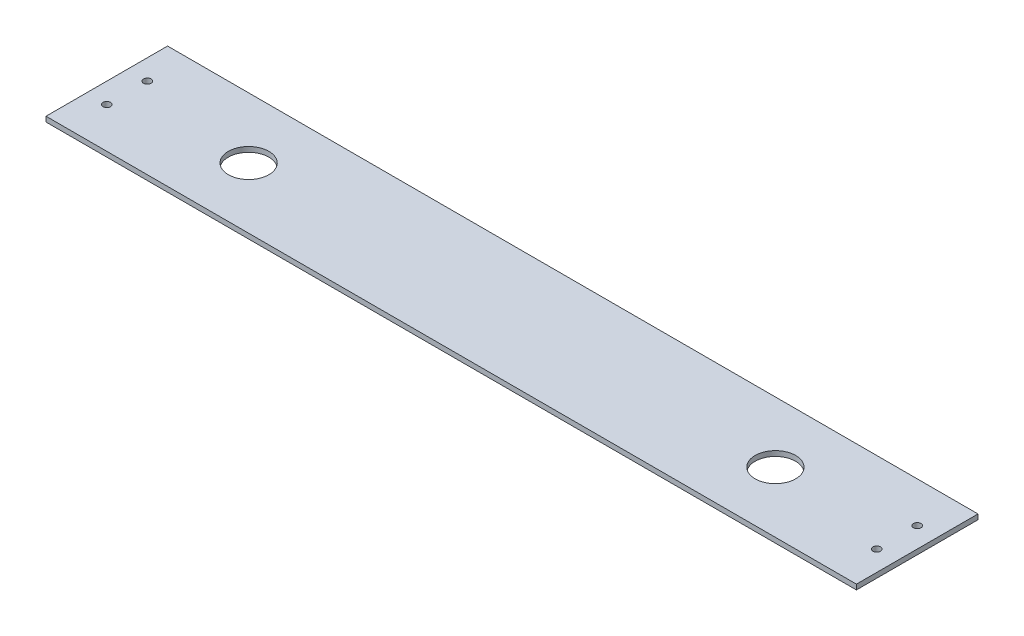
SolidWorks part; units mm, degrees
material "6061 Alloy"
ref_plane "Front Plane" through (0, 0, 0) normal (0, 0, 1) x (1, 0, 0)
ref_plane "Top Plane" through (0, 0, 0) normal (0, 1, 0) x (1, 0, 0)
ref_plane "Right Plane" through (0, 0, 0) normal (1, 0, 0) x (0, 0, -1)
sketch "Sketch1" plane through (0, 0, 0) normal (0, 1, 0) x (1, 0, 0)
  line L1 (254, -38.1) -> (-254, -38.1)
  line L2 (254, -38.1) -> (254, 38.1)
  line L3 (254, 38.1) -> (-254, 38.1)
  line L4 (-254, -38.1) -> (-254, 38.1)
  line L5 (254, -38.1) -> (-254, 38.1) construction
  line L6 (254, 38.1) -> (-254, -38.1) construction
  point P0 (0, 0)
  dimension "D1" = 508
  dimension "D2" = 76.2
extrude "Boss-Extrude1" add sketch "Sketch1" along normal blind 3.175
sketch "Sketch3" plane through (0, 3.175, 0) normal (0, 1, 0) x (1, 0, 0)
  line L1 (-241.3, 38.1) -> (-241.3, 12.7) construction
  line L2 (254, 38.1) -> (-254, 38.1) construction
  line L3 (-241.3, 12.7) -> (-241.3, -12.7) construction
  line L4 (-241.3, -12.7) -> (-241.3, -38.1) construction
  line L5 (-254, -38.1) -> (254, -38.1) construction
  line L6 (-254, 38.1) -> (-254, -38.1) construction
  line L7 (-254, 38.1) -> (254, 38.1) construction
  line L8 (0, 38.1) -> (0, -38.1) construction
  line L9 (241.3, -12.7) -> (241.3, -38.1) construction
  line L10 (241.3, 12.7) -> (241.3, -12.7) construction
  line L11 (241.3, 38.1) -> (241.3, 12.7) construction
  circle A0 centre (-241.3, 12.7) radius 2.3813
  circle A1 centre (-241.3, -12.7) radius 2.3813
  circle A2 centre (241.3, -12.7) radius 2.3813
  circle A3 centre (241.3, 12.7) radius 2.3813
  dimension "D2" = 25.4
  dimension "D3" = 4.7625
  dimension "D1" = 12.7
extrude "Cut-Extrude2" cut sketch "Sketch3" against normal blind 3.175
sketch "Sketch4" plane through (0, 3.175, 0) normal (0, 1, 0) x (1, 0, 0)
  line L0 (-254, 0) -> (-165.1, 0) construction
  line L1 (-254, 38.1) -> (-254, -38.1) construction
  line L2 (0, 38.1) -> (0, -38.1) construction
  line L3 (254, 38.1) -> (-254, 38.1) construction
  line L4 (-254, -38.1) -> (254, -38.1) construction
  line L5 (254, 0) -> (165.1, 0) construction
  circle A0 centre (-165.1, 0) radius 12.7
  circle A1 centre (165.1, 0) radius 12.7
  dimension "D1" = 25.4
  dimension "D2" = 88.9
extrude "Cut-Extrude3" cut sketch "Sketch4" against normal through all both
